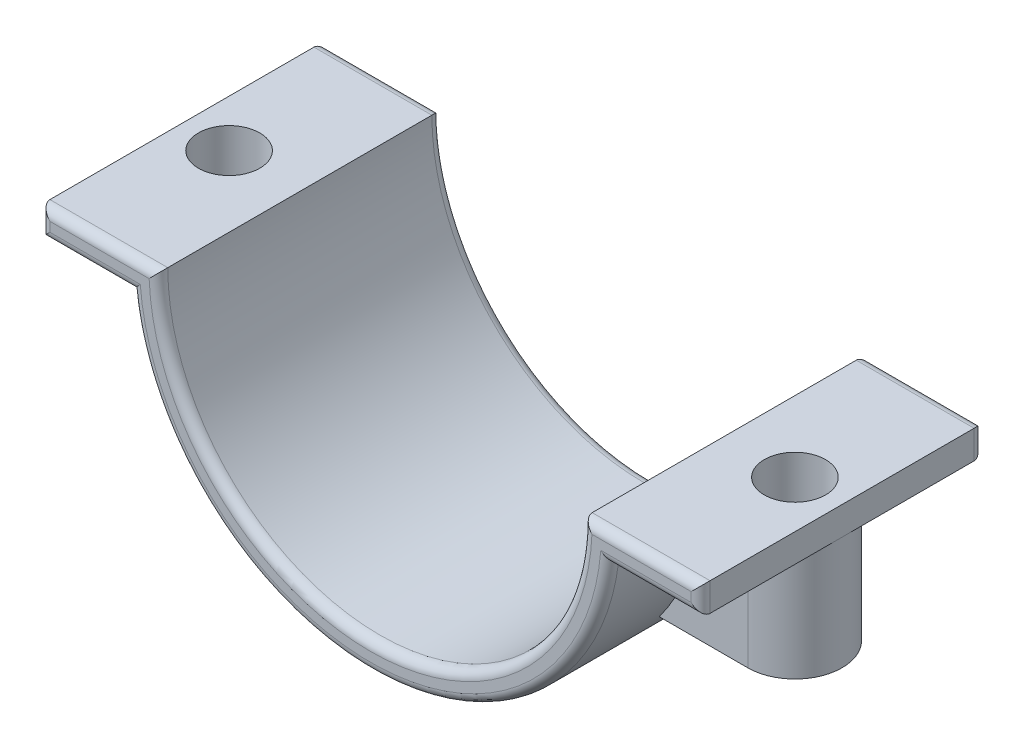
SolidWorks part; units mm, degrees
ref_plane "Front Plane" through (0, 0, 0) normal (0, 0, 1) x (1, 0, 0)
ref_plane "Top Plane" through (0, 0, 0) normal (0, 1, 0) x (1, 0, 0)
ref_plane "Right Plane" through (0, 0, 0) normal (1, 0, 0) x (0, 0, -1)
sketch "Sketch1" plane through (0, 0, 0) normal (0, 0, 1) x (1, 0, 0)
  line L0 (-35, 0) -> (-22.5, 0)
  line L1 (22.5, 0) -> (35, 0)
  line L2 (-35, -3) -> (-25.3229, -3)
  line L3 (25.3229, -3) -> (35, -3)
  line L4 (-35, 0) -> (-35, -3)
  line L5 (35, 0) -> (35, -3)
  arc A0 (-22.5, 0) -> (22.5, 0) centre (0, 0) ccw
  arc A1 (-25.3229, -3) -> (25.3229, -3) centre (0, 0) ccw
  point P6 (0, 0)
  dimension "D1" = 45
  dimension "D2" = 35
  dimension "D3" = 3
extrude "Boss-Extrude1" add sketch "Sketch1" along normal mid plane 30
sketch "Sketch2" plane through (0, -3, 0) normal (0, -1, 0) x (1, 0, 0)
  line L1 (18, 5) -> (30, 5)
  line L2 (18, 5) -> (18, -5)
  line L3 (18, -5) -> (30, -5)
  line L4 (30, 5) -> (30, -5)
  line L5 (18, 5) -> (30, -5) construction
  line L6 (18, -5) -> (30, 5) construction
  line L7 (35, 15) -> (35, -15) construction
  circle A0 centre (30, 0) radius 5
  circle A1 centre (30, 0) radius 3.25
  point P0 (24, 0)
  line M4 (25.3229, 15) -> (25.3229, -15)
  dimension "D1" = 10
  dimension "D2" = 6.5
  dimension "12" = 12
extrude "Boss-Extrude2" add sketch "Sketch2" against normal up to body from offset 12 contours A1 L4 A0 M4 | A1 L4 A0 | L4 A1 | L4 A1 | L3 L4 L1 L2 region at (33.4565, -3, 3.4565) region at (29.8896, -3, 4.125) region at (31.3793, -3, 0) region at (28.6207, -3, 0)
extrude "Cut-Extrude1" cut sketch "Sketch2<3>" against normal through all both and the other way through all contours L4 A1 | L4 A1 region at (31.3793, -3, 0) region at (28.6207, -3, 0)
sketch "Sketch2<3>" plane through (0, -3, 0) normal (0, -1, 0) x (1, 0, 0) same geometry as "Sketch2"
mirror "Mirror1" about plane through (0, 0, 0) normal (1, 0, 0) of "Boss-Extrude2", "Cut-Extrude1"
fillet "Fillet1" radius 1 16 edges at (28.75, 0, 15) (35, -1.5, 15) (30.1615, -3, 15) (0, -25.5, 15) (-30.1615, -3, 15) (-35, -1.5, 15) (-28.75, 0, 15) (0, -22.5, 15) (-28.75, 0, -15) (-35, -1.5, -15) (-30.1615, -3, -15) (0, -25.5, -15) (30.1615, -3, -15) (35, -1.5, -15) (28.75, 0, -15) (0, -22.5, -15)
